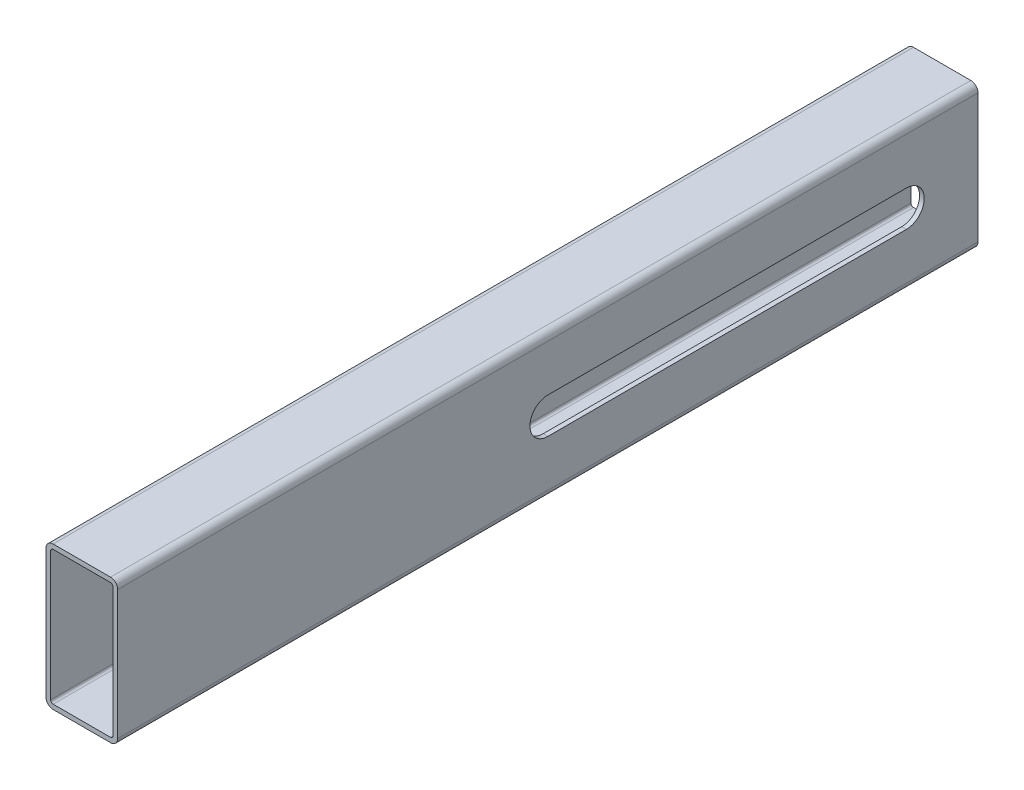
SolidWorks part; units mm, degrees
material "6061-T6 (SS)"
ref_plane "Front Plane" through (0, 0, 0) normal (0, 0, 1) x (1, 0, 0)
ref_plane "Top Plane" through (0, 0, 0) normal (0, 1, 0) x (1, 0, 0)
ref_plane "Right Plane" through (0, 0, 0) normal (1, 0, 0) x (0, 0, -1)
sketch "Sketch1" plane through (0, 0, 0) normal (0, 0, 1) x (1, 0, 0)
  line L1 (10.16, -25.4) -> (-10.16, -25.4)
  line L2 (12.7, -22.86) -> (12.7, 22.86)
  line L3 (10.16, 25.4) -> (-10.16, 25.4)
  line L4 (-12.7, -22.86) -> (-12.7, 22.86)
  line L5 (12.7, -25.4) -> (-12.7, 25.4) construction
  line L6 (12.7, 25.4) -> (-12.7, -25.4) construction
  arc A0 (-10.16, -25.4) -> (-12.7, -22.86) centre (-10.16, -22.86) cw
  arc A1 (10.16, -25.4) -> (12.7, -22.86) centre (10.16, -22.86) ccw
  arc A2 (12.7, 22.86) -> (10.16, 25.4) centre (10.16, 22.86) ccw
  arc A3 (-10.16, 25.4) -> (-12.7, 22.86) centre (-10.16, 22.86) ccw
  point P0 (0, 0)
  dimension "D3" = 2.54
  dimension "D1" = 25.4
  dimension "D2" = 50.8
extrude "Extrude-Thin1" add sketch "Sketch1" along normal blind 304.8 thin thin type one direction reverse wall 1.651
sketch "Sketch2" plane through (-12.7, 0, 0) normal (-1, 0, 0) x (0, 0, 1)
  line L0 (25.4, 0) -> (152.4, 0) construction
  line L1 (25.4, 6.35) -> (152.4, 6.35)
  line L2 (25.4, -6.35) -> (152.4, -6.35)
  line L3 (0, 22.86) -> (0, -22.86) construction
  arc A0 (25.4, 6.35) -> (25.4, -6.35) centre (25.4, 0) ccw
  arc A1 (152.4, -6.35) -> (152.4, 6.35) centre (152.4, 0) ccw
  point P3 (88.9, 0)
  dimension "D1" = 12.7
  dimension "D2" = 127
  dimension "D3" = 25.4
extrude "Cut-Extrude1" cut sketch "Sketch2" against normal through all
sketch "Sketch3" [suppressed] plane through (-12.7, 0, 0) normal (-1, 0, 0) x (0, 0, 1)
  line L0 (571.5, 0) -> (444.5, 0) construction
  line L1 (571.5, -6.35) -> (444.5, -6.35)
  line L2 (571.5, 6.35) -> (444.5, 6.35)
  line L3 (736.6, 22.86) -> (736.6, -22.86) construction
  arc A0 (571.5, -6.35) -> (571.5, 6.35) centre (571.5, 0) ccw
  arc A1 (444.5, 6.35) -> (444.5, -6.35) centre (444.5, 0) ccw
  point P3 (508, 0)
  dimension "D1" = 12.7
  dimension "D2" = 165.1
  dimension "D3" = 127
extrude "Cut-Extrude2" [suppressed] cut sketch "Sketch3" against normal through all
